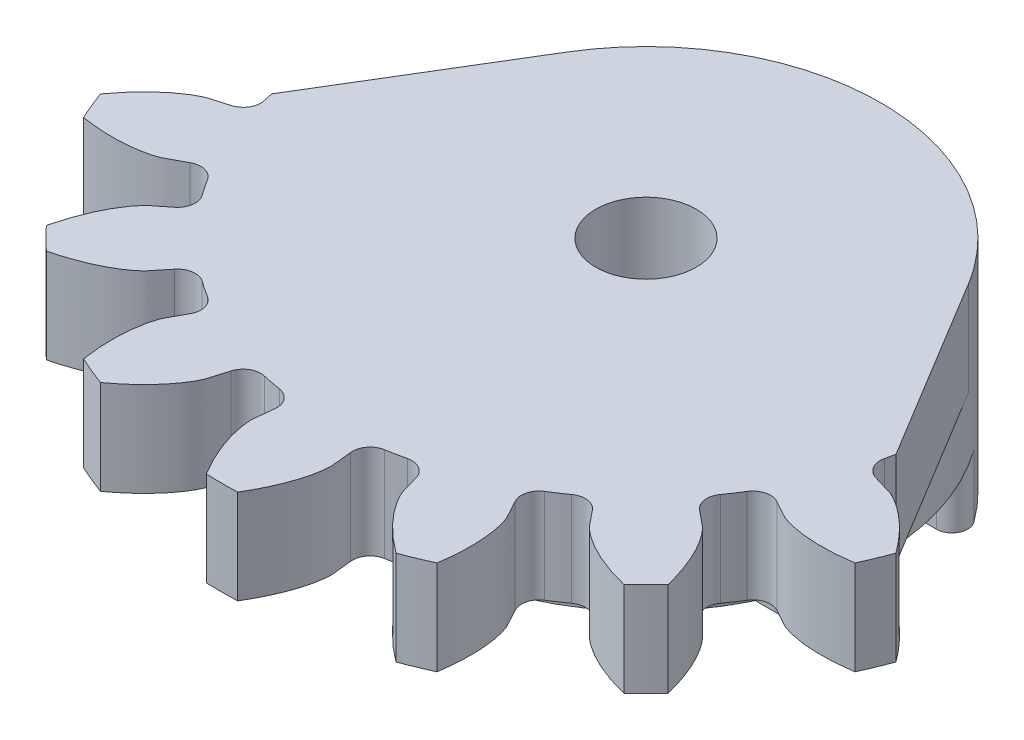
SolidWorks part; units mm, degrees
ref_plane "前视基准面" through (0, 0, 0) normal (0, 0, 1) x (1, 0, 0)
ref_plane "上视基准面" through (0, 0, 0) normal (0, 1, 0) x (1, 0, 0)
ref_plane "右视基准面" through (0, 0, 0) normal (1, 0, 0) x (0, 0, -1)
ref_plane "基准面1" through (0, -3, 0) normal (0, -1, 0) x (1, 0, 0)
sketch "草图1" plane through (0, -3, 0) normal (0, -1, 0) x (1, 0, 0)
  line L0 (-9.9305, 1.9753) -> (-6.3891, -3.8705)
  line L1 (6.3891, -3.8705) -> (9.9305, 1.9753)
  arc A0 (12.6547, 4.7019) -> (-12.6547, 4.7019) centre (0, 0) ccw
  arc A1 (-9.7317, 2.7944) -> (-9.9305, 1.9753) centre (0, 0) ccw
  arc A2 (-6.3891, -3.8705) -> (6.3891, -3.8705) centre (0, 0) ccw
  arc A3 (9.9305, 1.9753) -> (9.7317, 2.7944) centre (0, 0) ccw
  spline S0 degree 3 poles (-9.7317, 2.7944) (-10.2368, 2.9376) (-10.838, 3.1081) (-10.8878, 3.1299) (-10.9608, 3.1602) (-11.0465, 3.2026) (-11.1585, 3.2643) (-11.2901, 3.3458) (-11.441, 3.4501) (-11.6087, 3.5788) (-11.7913, 3.7341) (-11.9865, 3.9176) (-12.1918, 4.1309) (-12.4046, 4.3758) (-12.5595, 4.5716) (-12.6428, 4.6853) (-12.6547, 4.7019) knots 0 0 0 0 0.157982 0.188074 0.226923 0.272889 0.325009 0.382631 0.445272 0.512559 0.584192 0.659921 0.739537 0.822857 0.909725 0.924382 0.924382 0.924382 0.924382
  spline S1 degree 3 poles (9.7317, 2.7944) (10.2368, 2.9376) (10.838, 3.1081) (10.8878, 3.1299) (10.9608, 3.1602) (11.0465, 3.2026) (11.1585, 3.2643) (11.2901, 3.3458) (11.441, 3.4501) (11.6087, 3.5788) (11.7913, 3.7341) (11.9865, 3.9176) (12.1918, 4.1309) (12.4046, 4.3758) (12.5595, 4.5716) (12.6428, 4.6853) (12.6547, 4.7019) knots 0 0 0 0 0.157982 0.188074 0.226923 0.272889 0.325009 0.382631 0.445272 0.512559 0.584192 0.659921 0.739537 0.822857 0.909725 0.924382 0.924382 0.924382 0.924382
extrude "凸台-拉伸1" add sketch "草图1" against normal blind 3
sketch "草图2" plane through (0, -3, 0) normal (0, -1, 0) x (1, 0, 0)
  circle A0 centre (0, 0) radius 7.47
extrude "凸台-拉伸2" add sketch "草图2" along normal blind 2
sketch "草图3" plane through (0, 0, 0) normal (0, 1, 0) x (-1, 0, 0)
  arc A0 (-8.8573, 4.9054) -> (-7.9216, 6.3059) centre (0, 0) cw
  arc A1 (-9.8921, 9.1867) -> (-12.273, 5.6235) centre (0, 0) ccw
  spline S0 degree 3 poles (-8.8573, 4.9054) (-9.3157, 5.1613) (-9.8614, 5.4659) (-9.9121, 5.4857) (-9.985, 5.5158) (-10.0757, 5.5465) (-10.1984, 5.5821) (-10.3492, 5.6174) (-10.5295, 5.6504) (-10.7392, 5.678) (-10.9781, 5.6973) (-11.2459, 5.7056) (-11.5419, 5.6999) (-11.8655, 5.6772) (-12.1136, 5.6483) (-12.2528, 5.6267) (-12.273, 5.6235) knots 0 0 0 0 0.157982 0.188074 0.226923 0.272889 0.325009 0.382631 0.445272 0.512559 0.584192 0.659921 0.739537 0.822857 0.909725 0.924382 0.924382 0.924382 0.924382
  spline S1 degree 3 poles (-7.9216, 6.3059) (-8.3334, 6.6314) (-8.8236, 7.019) (-8.8613, 7.0583) (-8.9171, 7.1141) (-8.9801, 7.1862) (-9.06, 7.286) (-9.1503, 7.4117) (-9.2498, 7.5657) (-9.3555, 7.7489) (-9.4648, 7.9622) (-9.5749, 8.2064) (-9.683, 8.4821) (-9.7858, 8.7898) (-9.854, 9.03) (-9.8874, 9.1669) (-9.8921, 9.1867) knots 0 0 0 0 0.157982 0.188074 0.226923 0.272889 0.325009 0.382631 0.445272 0.512559 0.584192 0.659921 0.739537 0.822857 0.909725 0.924382 0.924382 0.924382 0.924382
extrude "切除-拉伸1" cut sketch "草图3" against normal through all
sketch "草图4" plane through (0, 0, 0) normal (0, 1, 0) x (-1, 0, 0)
  arc A0 (-6.3059, 7.9216) -> (-4.9054, 8.8573) centre (0, 0) cw
  arc A1 (-5.6235, 12.273) -> (-9.1867, 9.8921) centre (0, 0) ccw
  spline S0 degree 3 poles (-6.3059, 7.9216) (-6.6314, 8.3334) (-7.019, 8.8236) (-7.0583, 8.8613) (-7.1141, 8.9171) (-7.1862, 8.9801) (-7.286, 9.06) (-7.4117, 9.1503) (-7.5657, 9.2498) (-7.7489, 9.3555) (-7.9622, 9.4648) (-8.2064, 9.5749) (-8.4821, 9.683) (-8.7898, 9.7858) (-9.03, 9.854) (-9.1669, 9.8874) (-9.1867, 9.8921) knots 0 0 0 0 0.157982 0.188074 0.226923 0.272889 0.325009 0.382631 0.445272 0.512559 0.584192 0.659921 0.739537 0.822857 0.909725 0.924382 0.924382 0.924382 0.924382
  spline S1 degree 3 poles (-4.9054, 8.8573) (-5.1613, 9.3157) (-5.4659, 9.8614) (-5.4857, 9.9121) (-5.5158, 9.985) (-5.5465, 10.0757) (-5.5821, 10.1984) (-5.6174, 10.3492) (-5.6504, 10.5295) (-5.678, 10.7392) (-5.6973, 10.9781) (-5.7056, 11.2459) (-5.6999, 11.5419) (-5.6772, 11.8655) (-5.6483, 12.1136) (-5.6267, 12.2528) (-5.6235, 12.273) knots 0 0 0 0 0.157982 0.188074 0.226923 0.272889 0.325009 0.382631 0.445272 0.512559 0.584192 0.659921 0.739537 0.822857 0.909725 0.924382 0.924382 0.924382 0.924382
extrude "切除-拉伸2" cut sketch "草图4" against normal through all
sketch "草图5" plane through (0, 0, 0) normal (0, 1, 0) x (-1, 0, 0)
  arc A0 (-2.7944, 9.7317) -> (-1.1425, 10.0603) centre (0, 0) cw
  arc A1 (-0.4988, 13.4908) -> (-4.7019, 12.6547) centre (0, 0) ccw
  spline S0 degree 3 poles (-2.7944, 9.7317) (-2.9376, 10.2368) (-3.1081, 10.838) (-3.1299, 10.8878) (-3.1602, 10.9608) (-3.2026, 11.0465) (-3.2643, 11.1585) (-3.3458, 11.2901) (-3.4501, 11.441) (-3.5788, 11.6087) (-3.7341, 11.7913) (-3.9176, 11.9865) (-4.1309, 12.1918) (-4.3758, 12.4046) (-4.5716, 12.5595) (-4.6853, 12.6428) (-4.7019, 12.6547) knots 0 0 0 0 0.157982 0.188074 0.226923 0.272889 0.325009 0.382631 0.445272 0.512559 0.584192 0.659921 0.739537 0.822857 0.909725 0.924382 0.924382 0.924382 0.924382
  spline S1 degree 3 poles (-1.1425, 10.0603) (-1.2035, 10.5817) (-1.276, 11.2024) (-1.2749, 11.2568) (-1.2749, 11.3358) (-1.2685, 11.4313) (-1.2544, 11.5583) (-1.2294, 11.7111) (-1.1908, 11.8904) (-1.1361, 12.0946) (-1.0625, 12.3227) (-0.9676, 12.5733) (-0.8492, 12.8446) (-0.7043, 13.1349) (-0.5827, 13.353) (-0.5095, 13.4734) (-0.4988, 13.4908) knots 0 0 0 0 0.157982 0.188074 0.226923 0.272889 0.325009 0.382631 0.445272 0.512559 0.584192 0.659921 0.739537 0.822857 0.909725 0.924382 0.924382 0.924382 0.924382
extrude "切除-拉伸3" cut sketch "草图5" against normal through all
sketch "草图6" plane through (0, 0, 0) normal (0, 1, 0) x (-1, 0, 0)
  arc A0 (1.1425, 10.0603) -> (2.7944, 9.7317) centre (0, 0) cw
  arc A1 (4.7019, 12.6547) -> (0.4988, 13.4908) centre (0, 0) ccw
  spline S0 degree 3 poles (1.1425, 10.0603) (1.2035, 10.5817) (1.276, 11.2024) (1.2749, 11.2568) (1.2749, 11.3358) (1.2685, 11.4313) (1.2544, 11.5583) (1.2294, 11.7111) (1.1908, 11.8904) (1.1361, 12.0946) (1.0625, 12.3227) (0.9676, 12.5733) (0.8492, 12.8446) (0.7043, 13.1349) (0.5827, 13.353) (0.5095, 13.4734) (0.4988, 13.4908) knots 0 0 0 0 0.157982 0.188074 0.226923 0.272889 0.325009 0.382631 0.445272 0.512559 0.584192 0.659921 0.739537 0.822857 0.909725 0.924382 0.924382 0.924382 0.924382
  spline S1 degree 3 poles (2.7944, 9.7317) (2.9376, 10.2368) (3.1081, 10.838) (3.1299, 10.8878) (3.1602, 10.9608) (3.2026, 11.0465) (3.2643, 11.1585) (3.3458, 11.2901) (3.4501, 11.441) (3.5788, 11.6087) (3.7341, 11.7913) (3.9176, 11.9865) (4.1309, 12.1918) (4.3758, 12.4046) (4.5716, 12.5595) (4.6853, 12.6428) (4.7019, 12.6547) knots 0 0 0 0 0.157982 0.188074 0.226923 0.272889 0.325009 0.382631 0.445272 0.512559 0.584192 0.659921 0.739537 0.822857 0.909725 0.924382 0.924382 0.924382 0.924382
extrude "切除-拉伸4" cut sketch "草图6" against normal through all
sketch "草图7" plane through (0, 0, 0) normal (0, 1, 0) x (-1, 0, 0)
  arc A0 (4.9054, 8.8573) -> (6.3059, 7.9216) centre (0, 0) cw
  arc A1 (9.1867, 9.8921) -> (5.6235, 12.273) centre (0, 0) ccw
  spline S0 degree 3 poles (4.9054, 8.8573) (5.1613, 9.3157) (5.4659, 9.8614) (5.4857, 9.9121) (5.5158, 9.985) (5.5465, 10.0757) (5.5821, 10.1984) (5.6174, 10.3492) (5.6504, 10.5295) (5.678, 10.7392) (5.6973, 10.9781) (5.7056, 11.2459) (5.6999, 11.5419) (5.6772, 11.8655) (5.6483, 12.1136) (5.6267, 12.2528) (5.6235, 12.273) knots 0 0 0 0 0.157982 0.188074 0.226923 0.272889 0.325009 0.382631 0.445272 0.512559 0.584192 0.659921 0.739537 0.822857 0.909725 0.924382 0.924382 0.924382 0.924382
  spline S1 degree 3 poles (6.3059, 7.9216) (6.6314, 8.3334) (7.019, 8.8236) (7.0583, 8.8613) (7.1141, 8.9171) (7.1862, 8.9801) (7.286, 9.06) (7.4117, 9.1503) (7.5657, 9.2498) (7.7489, 9.3555) (7.9622, 9.4648) (8.2064, 9.5749) (8.4821, 9.683) (8.7898, 9.7858) (9.03, 9.854) (9.1669, 9.8874) (9.1867, 9.8921) knots 0 0 0 0 0.157982 0.188074 0.226923 0.272889 0.325009 0.382631 0.445272 0.512559 0.584192 0.659921 0.739537 0.822857 0.909725 0.924382 0.924382 0.924382 0.924382
extrude "切除-拉伸5" cut sketch "草图7" against normal through all
sketch "草图8" plane through (0, 0, 0) normal (0, 1, 0) x (-1, 0, 0)
  arc A0 (7.9216, 6.3059) -> (8.8573, 4.9054) centre (0, 0) cw
  arc A1 (12.273, 5.6235) -> (9.8921, 9.1867) centre (0, 0) ccw
  spline S0 degree 3 poles (7.9216, 6.3059) (8.3334, 6.6314) (8.8236, 7.019) (8.8613, 7.0583) (8.9171, 7.1141) (8.9801, 7.1862) (9.06, 7.286) (9.1503, 7.4117) (9.2498, 7.5657) (9.3555, 7.7489) (9.4648, 7.9622) (9.5749, 8.2064) (9.683, 8.4821) (9.7858, 8.7898) (9.854, 9.03) (9.8874, 9.1669) (9.8921, 9.1867) knots 0 0 0 0 0.157982 0.188074 0.226923 0.272889 0.325009 0.382631 0.445272 0.512559 0.584192 0.659921 0.739537 0.822857 0.909725 0.924382 0.924382 0.924382 0.924382
  spline S1 degree 3 poles (8.8573, 4.9054) (9.3157, 5.1613) (9.8614, 5.4659) (9.9121, 5.4857) (9.985, 5.5158) (10.0757, 5.5465) (10.1984, 5.5821) (10.3492, 5.6174) (10.5295, 5.6504) (10.7392, 5.678) (10.9781, 5.6973) (11.2459, 5.7056) (11.5419, 5.6999) (11.8655, 5.6772) (12.1136, 5.6483) (12.2528, 5.6267) (12.273, 5.6235) knots 0 0 0 0 0.157982 0.188074 0.226923 0.272889 0.325009 0.382631 0.445272 0.512559 0.584192 0.659921 0.739537 0.822857 0.909725 0.924382 0.924382 0.924382 0.924382
extrude "切除-拉伸6" cut sketch "草图8" against normal through all
sketch "草图9" plane through (0, -5, 0) normal (0, -1, 0) x (1, 0, 0)
  line L0 (3, 1.25) -> (6, 1.25)
  line L1 (6, 1.25) -> (6, -1.25)
  line L2 (6, -1.25) -> (3, -1.25)
  line L3 (3, -1.25) -> (3, 1.25)
extrude "凸台-拉伸3" add sketch "草图9" along normal blind 2
sketch "草图10" plane through (0, -5, 0) normal (0, -1, 0) x (1, 0, 0)
  line L0 (-5.6366, -3.6) -> (5.6366, -3.6)
  arc A0 (5.6366, -3.6) -> (6.0409, -4.3941) centre (5.6366, -4.1) cw
  arc A1 (6.0409, -4.3941) -> (-6.0409, -4.3941) centre (0, 0) cw
  arc A2 (-6.0409, -4.3941) -> (-5.6366, -3.6) centre (-5.6366, -4.1) cw
extrude "凸台-拉伸4" add sketch "草图10" along normal blind 2
sketch "草图11" plane through (0, -5, 0) normal (0, -1, 0) x (1, 0, 0)
  line L0 (-3, -1.25) -> (-6, -1.25)
  line L1 (-6, -1.25) -> (-6, 1.25)
  line L2 (-6, 1.25) -> (-3, 1.25)
  line L3 (-3, 1.25) -> (-3, -1.25)
extrude "凸台-拉伸5" add sketch "草图11" along normal blind 2
hole_wizard "Ø3.2 (3.2) 直径孔1" positions "草图13" profile "草图12" hole size "Ø3.2" standard "ANSI Metric"
sketch "草图13" plane through (0, -5, 0) normal (0, -1, 0) x (1, 0, 0)
  point P0 (0, 0)
sketch "草图12" plane through (0, -5, 0) normal (1, 0, 0) x (0, 0, -1)
  line L0 (0, 0) -> (0, 5)
  line L1 (0, 5) -> (1.6, 5)
  line L2 (1.6, 5) -> (1.6, 0)
  line L5 (1.6, 0) -> (0, 0)
  line L11 (0, -6.35) -> (0, 107.95) construction
  dimension "通孔孔直径" = 3.2
  dimension "通孔孔深度" = 5
fillet "圆角1" radius 0.5614 14 edges at (-1.1425, -1.5, 10.0603) (-7.9216, -1.5, 6.3059) (-4.9054, -1.5, 8.8573) (8.8573, -1.5, 4.9054) (-9.7317, -1.5, 2.7944) (7.9216, -1.5, 6.3059) (-2.7944, -1.5, 9.7317) (6.3059, -1.5, 7.9216) (-6.3059, -1.5, 7.9216) (4.9054, -1.5, 8.8573) (-8.8573, -1.5, 4.9054) (2.7944, -1.5, 9.7317) (9.7317, -1.5, 2.7944) (1.1425, -1.5, 10.0603) tangent propagation no
